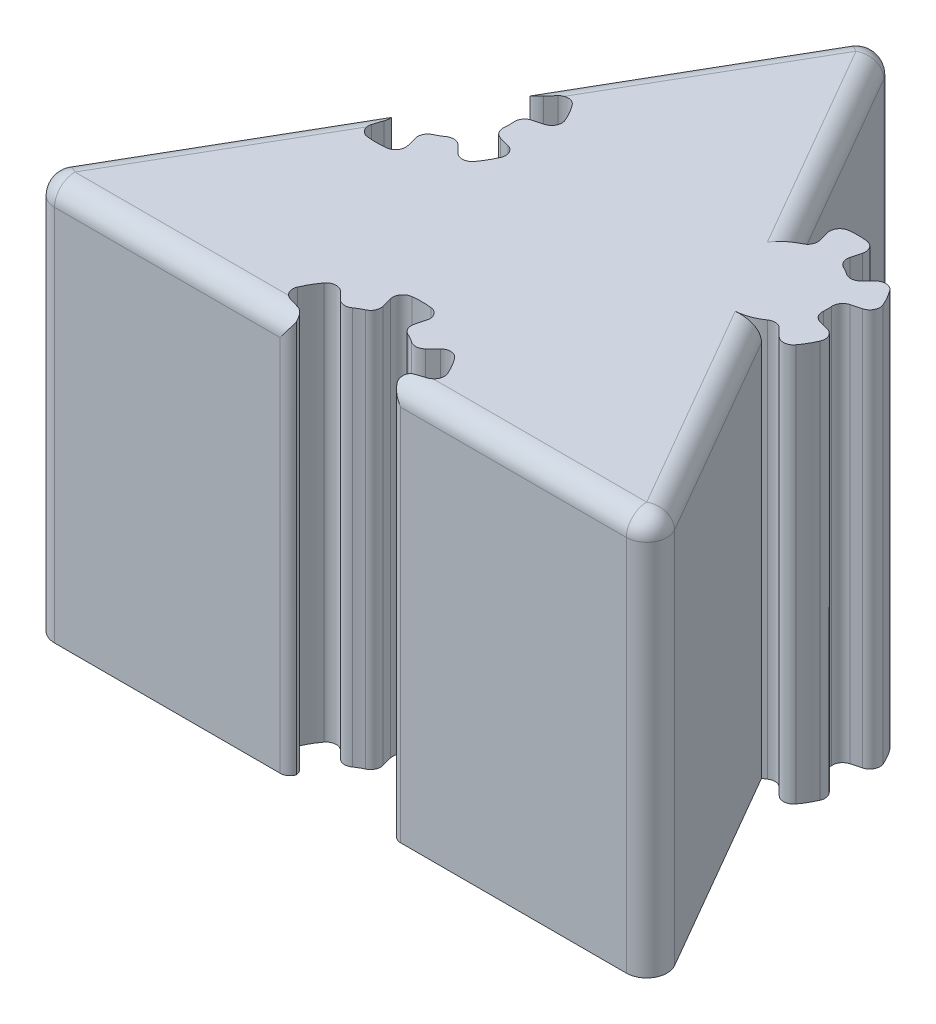
SolidWorks part; units mm, degrees
ref_plane "Front Plane" through (0, 0, 0) normal (0, 0, 1) x (1, 0, 0)
ref_plane "Top Plane" through (0, 0, 0) normal (0, 1, 0) x (1, 0, 0)
ref_plane "Right Plane" through (0, 0, 0) normal (1, 0, 0) x (0, 0, -1)
sketch "Sketch1" plane through (0, 0, 0) normal (0, 1, 0) x (1, 0, 0)
  line L1 (0, 15.75) -> (-15.75, -11.5298)
  line L2 (-15.75, -11.5298) -> (15.75, -11.5298)
  line L3 (15.75, -11.5298) -> (0, 15.75)
extrude "Boss-Extrude1" add sketch "Sketch1" along normal blind 19.5
sketch "Sketch2" plane through (0, 19.5, 0) normal (0, 1, 0) x (1, 0, 0)
  line L0 (0, 15.75) -> (-15.75, -11.5298) construction
  line L1 (15.75, -11.5298) -> (0, 15.75) construction
  line L2 (-15.75, -11.5298) -> (15.75, -11.5298) construction
  line L3 (-9.875, -1.354) -> (-5.875, 5.5742)
  line L4 (-6.1072, 3.8779) -> (-5.0466, 4.9385)
  line L5 (5.9375, 5.4659) -> (9.8125, -1.2457)
  line L6 (-5.4602, 2.7571) -> (-4.0113, 3.1454)
  line L7 (4, -11.5298) -> (-4, -11.5298)
  line L8 (-5.4602, 1.4631) -> (-4.0113, 1.0748)
  line L9 (-6.1072, 0.3423) -> (-5.0466, -0.7183)
  line L10 (-7.228, -0.3047) -> (-6.8397, -1.7536)
  line L11 (-8.522, -0.3047) -> (-8.9103, -1.7536)
  line L12 (-2.4148, -10.8828) -> (-3.8637, -10.4945)
  line L13 (-1.7678, -9.762) -> (-2.8284, -8.7014)
  line L14 (-0.647, -9.115) -> (-1.0353, -7.6661)
  line L15 (0.647, -9.115) -> (1.0353, -7.6661)
  line L16 (1.7678, -9.762) -> (2.8284, -8.7014)
  line L17 (2.4148, -10.8828) -> (3.8637, -10.4945)
  line L18 (7.2603, 4.4042) -> (6.8721, 5.8531)
  line L19 (8.4897, 4.4042) -> (8.8779, 5.8531)
  line L20 (9.5544, 3.7895) -> (10.615, 4.8501)
  line L21 (10.1691, 2.7248) -> (11.618, 3.113)
  line L22 (9.5544, 0.4307) -> (10.615, -0.6299)
  line L23 (10.1691, 1.4954) -> (11.618, 1.1072)
  arc A0 (-9.125, -0.055) -> (-8.522, -0.3047) centre (-7.875, 2.1101) ccw
  arc A1 (-9.875, -1.354) -> (-5.875, 5.5742) centre (-7.875, 2.1101) ccw
  arc A2 (9.8125, -1.2457) -> (5.9375, 5.4659) centre (7.875, 2.1101) ccw
  arc A3 (9.0625, 0.0533) -> (9.5544, 0.4307) centre (7.875, 2.1101) ccw
  arc A4 (2.5, -11.5298) -> (2.4148, -10.8828) centre (0, -11.5298) ccw
  arc A5 (4, -11.5298) -> (-4, -11.5298) centre (0, -11.5298) ccw
  arc A6 (-2.4148, -10.8828) -> (-2.5, -11.5298) centre (0, -11.5298) ccw
  arc A7 (-0.647, -9.115) -> (-1.7678, -9.762) centre (0, -11.5298) ccw
  arc A8 (1.7678, -9.762) -> (0.647, -9.115) centre (0, -11.5298) ccw
  arc A9 (-7.228, -0.3047) -> (-6.1072, 0.3423) centre (-7.875, 2.1101) ccw
  arc A10 (-5.4602, 1.4631) -> (-5.4602, 2.7571) centre (-7.875, 2.1101) ccw
  arc A11 (-6.1072, 3.8779) -> (-6.625, 4.2752) centre (-7.875, 2.1101) ccw
  arc A12 (7.2603, 4.4042) -> (6.6875, 4.1669) centre (7.875, 2.1101) ccw
  arc A13 (9.5544, 3.7895) -> (8.4897, 4.4042) centre (7.875, 2.1101) ccw
  arc A14 (10.1691, 1.4954) -> (10.1691, 2.7248) centre (7.875, 2.1101) ccw
  dimension "D1" = 15
  dimension "D2" = 30
  dimension "D3" = 30
  dimension "D4" = 15
  dimension "D5" = 30
  dimension "D6" = 30
  dimension "D19" = 2.375
  dimension "D20" = 3.875
  dimension "D21" = 4
  dimension "D22" = 2.5
  dimension "D23" = 4
  dimension "D7" = 15
  dimension "D8" = 30
  dimension "D9" = 30
  dimension "D10" = 30
  dimension "D11" = 30
  dimension "D12" = 30
  dimension "D13" = 15
  dimension "D14" = 30
  dimension "D15" = 30
  dimension "D16" = 30
  dimension "D17" = 30
  dimension "D18" = 30
extrude "Cut-Extrude1" cut sketch "Sketch2" against normal through all contours L4 A11 L3 A0 L11 A1 L10 A9 L9 L8 A10 L6 | L16 A8 L15 A5 L14 A7 L13 L12 A6 L7 A4 L17 region at (-6.5315, 19.5, -1.3344) region at (0, 19.5, 9.9784)
extrude "Boss-Extrude2" add sketch "Sketch2<3>" against normal through all contours L23 A14 L21 A2 L20 A13 L19 L18 A12 L5 A3 L22 region at (9.1768, 19.5, -2.8617)
sketch "Sketch2<3>" plane through (0, 19.5, 0) normal (0, 1, 0) x (1, 0, 0) same geometry as "Sketch2"
fillet "Fillet2" radius 0.5 40 edges at (7.2603, 9.75, -4.4042) (6.8721, 9.75, -5.8531) (8.8779, 9.75, -5.8531) (8.4897, 9.75, -4.4042) (9.5544, 9.75, -3.7895) (10.615, 9.75, -4.8501) (11.618, 9.75, -3.113) (10.1691, 9.75, -2.7248) (10.1691, 9.75, -1.4954) (11.618, 9.75, -1.1072) (10.615, 9.75, 0.6299) (9.5544, 9.75, -0.4307) (2.5, 9.75, 11.5298) (2.4148, 9.75, 10.8828) (3.8637, 9.75, 10.4945) (2.8284, 9.75, 8.7014) (1.7678, 9.75, 9.762) (1.0353, 9.75, 7.6661) (-1.0353, 9.75, 7.6661) (0.647, 9.75, 9.115) (-0.647, 9.75, 9.115) (-1.7678, 9.75, 9.762) (-2.8284, 9.75, 8.7014) (-3.8637, 9.75, 10.4945) (-2.4148, 9.75, 10.8828) (-2.5, 9.75, 11.5298) (-9.125, 9.75, 0.055) (-8.522, 9.75, 0.3047) (-8.9103, 9.75, 1.7536) (-6.8397, 9.75, 1.7536) (-5.0466, 9.75, 0.7183) (-4.0113, 9.75, -1.0748) (-7.228, 9.75, 0.3047) (-6.1072, 9.75, -0.3423) (-5.4602, 9.75, -1.4631) (-5.4602, 9.75, -2.7571) (-4.0113, 9.75, -3.1454) (-5.0466, 9.75, -4.9385) (-6.1072, 9.75, -3.8779) (-6.625, 9.75, -4.2752)
sketch "Sketch9" plane through (0, 0, 0) normal (0, -1, 0) x (1, 0, 0)
  line L5 (-0.5124, -13.8376) -> (-4.5826, -5.6029)
  line L6 (-3.6088, 0.0898) -> (-2.0405, 2.8063)
  line L7 (-1.2322, 4.2063) -> (0.2279, 6.7352)
  line L10 (-8.7095, 2.6168) -> (-13.8517, 10.3447)
  line L11 (-13.8517, 10.3447) -> (-4.5878, 10.1183)
  line L13 (-15.75, 11.5298) -> (-2.958, 11.5298) construction
  line L14 (7.1209, -0.6163) -> (13.3251, 10.1298)
  line L18 (-0.5124, -13.8376) -> (6.3126, -2.0163)
  line L19 (2.958, 11.5298) -> (15.75, 11.5298) construction
  line L20 (15.75, 11.5298) -> (9.0625, -0.0533) construction
  line L21 (4.5913, 10.1298) -> (13.3251, 10.1298)
  line L22 (-4.5407, 1.3428) -> (-1.3231, 6.9158)
  line L23 (-2.0405, 2.8063) -> (6.3126, -2.0163)
  line L25 (7.1209, -0.6163) -> (-1.2322, 4.2063)
  arc A1 (-4.5826, -5.6029) -> (-3.6088, 0.0898) centre (-7.875, -2.1101) ccw
  arc A3 (-4.5878, 10.1183) -> (-1.3231, 6.9158) centre (0, 11.5298) ccw
  arc A9 (-4.5407, 1.3428) -> (-8.7095, 2.6168) centre (-7.875, -2.1101) ccw
  arc A10 (0.2279, 6.7352) -> (4.5913, 10.1298) centre (0, 11.5298) ccw
  dimension "D1" = 4.8
  dimension "D2" = 1.4
  dimension "D3" = 4.8
  dimension "D4" = 1.4
  dimension "D5" = 1.4
  dimension "D7" = 1.4
fillet "Fillet4" radius 1 9 edges at (-15.75, 9.75, 11.5298) (15.75, 9.75, 11.5298) (0, 9.75, -15.75) (12.4062, 19.5, 5.7383) (3.3437, 19.5, -9.9585) (-3.198, 19.5, -10.2109) (-12.552, 19.5, 5.9907) (-9.354, 19.5, 11.5298) (9.354, 19.5, 11.5298)
extrude "Cut-Extrude6" cut sketch "Sketch9" against normal blind 17
